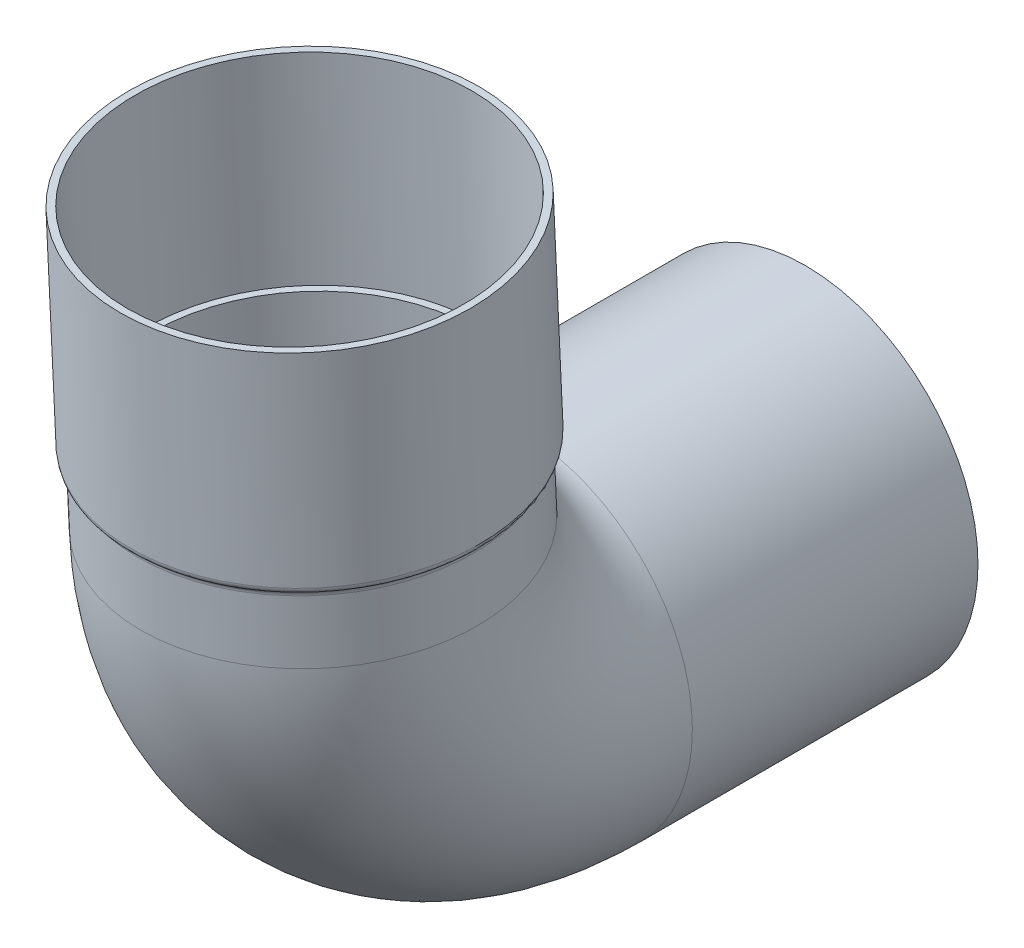
SolidWorks part; units mm, degrees
ref_plane "Plan de face" through (0, 0, 0) normal (0, 0, 1) x (1, 0, 0)
ref_plane "Plan de dessus" through (0, 0, 0) normal (0, 1, 0) x (1, 0, 0)
ref_plane "Plan de droite" through (0, 0, 0) normal (1, 0, 0) x (0, 0, -1)
sketch "Esquisse6" plane through (0, 0, 0) normal (0, 0, 1) x (1, 0, 0)
  circle A0 centre (0, 0) radius 25
sketch "Esquisse7" plane through (0, 0, 0) normal (1, 0, 0) x (0, 0, -1)
  line L0 (0, 0) -> (-41.3814, 0)
  line L1 (-71.3481, 28.5868) -> (-71.8372, 38.9567)
  arc A0 (-41.3814, 0) -> (-71.3481, 28.5868) centre (-41.3814, 30) cw
  point P6 (-70, 0)
  dimension "D4" = 30
  dimension "D1" = 39
  dimension "D2" = 70
  dimension "D3" = 87.3
sweep "Balayage-Mince2" add profiles "Esquisse6" path "Esquisse7" parameters "D1"=1
sketch "Esquisse8" plane through (0, 42.2505, 1.9925) normal (0, 0.9989, 0.0471) x (1, 0, 0)
  line L0 (-24, -69.9223) -> (24, -69.9223) construction
  line L1 (0, -45.9223) -> (0, -93.9223) construction
  circle A0 centre (0, -69.9223) radius 24 construction
  circle A1 centre (0, -69.9223) radius 24 construction
  circle A2 centre (0, -69.9223) radius 24
  point P10 (0, -69.9223)
extrude "Extru.-Mince1" add sketch "Esquisse8" along normal blind 1 separate body thin contours A2 thin type one direction wall 2
sketch "Esquisse9" plane through (0, 43.2494, 2.0396) normal (0, 0.9989, 0.0471) x (1, 0, 0)
  line L0 (-24, -69.9223) -> (24, -69.9223) construction
  line L1 (0, -45.9223) -> (0, -93.9223) construction
  circle A0 centre (0, -69.9223) radius 24 construction
  circle A1 centre (0, -69.9223) radius 24 construction
  circle A2 centre (0, -69.9223) radius 26
extrude "Extru.-Mince2" add sketch "Esquisse9" along normal blind 30 thin thin type one direction reverse wall 1
fillet "Congé1" radius 1 1 edges at (25, 38.9567, 71.8372)
fillet "Congé2" radius 1 1 edges at (26, 38.9567, 71.8372)
